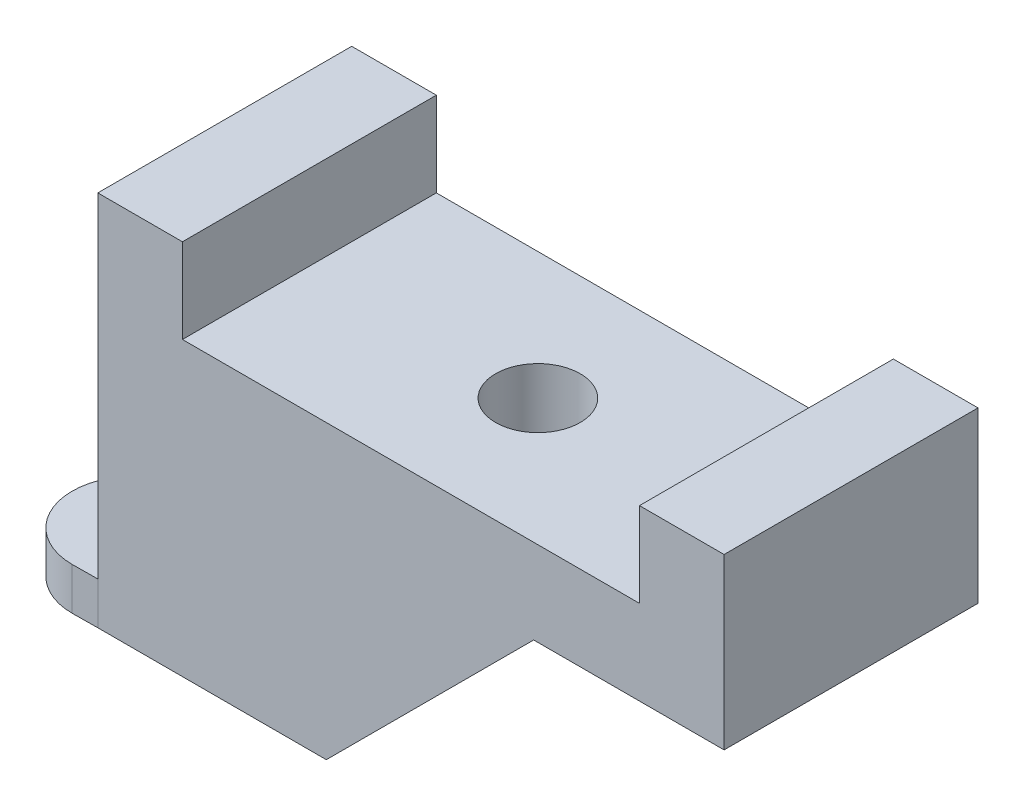
SolidWorks part; units mm, degrees
ref_plane "Front Plane" through (0, 0, 0) normal (0, 0, 1) x (1, 0, 0)
ref_plane "Top Plane" through (0, 0, 0) normal (0, 1, 0) x (1, 0, 0)
ref_plane "Right Plane" through (0, 0, 0) normal (1, 0, 0) x (0, 0, -1)
sketch "Sketch1" plane through (0, 0, 0) normal (0, 1, 0) x (1, 0, 0)
  line L1 (-11.1, 4.5) -> (11.1, 4.5)
  line L2 (-11.1, 4.5) -> (-11.1, -4.5)
  line L3 (-11.1, -4.5) -> (11.1, -4.5)
  line L4 (11.1, 4.5) -> (11.1, -4.5)
  line L5 (-11.1, 4.5) -> (11.1, -4.5) construction
  line L6 (-11.1, -4.5) -> (11.1, 4.5) construction
  circle A0 centre (0, 0) radius 1.5
  point P0 (0, 0)
  dimension "D3" = 3
  dimension "D1" = 9
  dimension "D2" = 22.2
extrude "Boss-Extrude1" add sketch "Sketch1" along normal blind 3
sketch "Sketch2" plane through (0, 3, 0) normal (0, 1, 0) x (1, 0, 0)
  line L0 (-11.1, -4.5) -> (11.1, -4.5) construction
  line L1 (-11.1, 4.5) -> (-8.1, 4.5)
  line L2 (-11.1, 4.5) -> (-11.1, -4.5)
  line L3 (-11.1, -4.5) -> (-8.1, -4.5)
  line L4 (-8.1, 4.5) -> (-8.1, -4.5)
  line L5 (11.1, 4.5) -> (-11.1, 4.5) construction
  line L6 (11.1, -4.5) -> (8.1, -4.5)
  line L7 (11.1, -4.5) -> (11.1, 4.5)
  line L8 (11.1, 4.5) -> (8.1, 4.5)
  line L9 (8.1, -4.5) -> (8.1, 4.5)
  dimension "D1" = 3
  dimension "D2" = 3
extrude "Boss-Extrude2" add sketch "Sketch2" along normal blind 3
sketch "Sketch3" plane through (0, 3, 0) normal (0, 1, 0) x (1, 0, 0)
  line L0 (-11.1, 0) -> (-12, -0.01)
  line L1 (-11.1, 4.5) -> (-11.1, -4.5) construction
  line L2 (-12, -0.01) -> (-12, -4.51)
  line L3 (-12, -4.51) -> (-11.1, -4.5)
  line L4 (-11.1, -4.5) -> (-11.1, 0)
  circle A0 centre (-12, -2.26) radius 0.75
  circle A1 centre (0, 0) radius 1.5 construction
  circle A2 centre (-12, -2.26) radius 2.25
  dimension "D3" = 1.5
  dimension "D4" = 4.5
  dimension "D1" = 12
  dimension "D2" = 2.26
extrude "Boss-Extrude3" add sketch "Sketch3" along normal blind 1.5 from offset 10.35 contours L3 A2 L4 L2 A0 | L2 A2 A0 | A2 L3 L4 | A2 L4 L0 region at (-11.3289, 3, 0.0615) region at (-11.5507, 3, -0.0587) region at (-11.5497, 3, 0.1024) region at (-13.0345, 3, 2.26) offset against normal yes
sketch "Sketch4" plane through (0, 0, 0) normal (0, -1, 0) x (1, 0, 0)
  line L0 (11.1, -4.5) -> (-11.1, -4.5) construction
  line L1 (-11.1, 4.5) -> (-3, 4.5)
  line L2 (-11.1, 4.5) -> (-11.1, -4.5)
  line L3 (-11.1, -4.5) -> (-3, -4.5)
  line L4 (-3, 4.5) -> (-3, -4.5)
  dimension "D1" = 3
extrude "Boss-Extrude4" add sketch "Sketch4" along normal up to surface (7.35 mm away) up to face at (-12, -7.35, 3.01)
chamfer "Chamfer1" distance 7.35 angle 45 1 edges at (-3, 0, 0)
chamfer "Chamfer2" distance 4.5 angle 45 1 edges at (-7.05, -7.35, -4.5)
sketch "Sketch5" plane through (0, 3, 0) normal (0, 1, 0) x (1, 0, 0)
  circle A0 centre (0, 0) radius 3
  dimension "D1" = 6
extrude "Cut-Extrude1" cut sketch "Sketch5" against normal through all from offset 3 offset against normal yes
